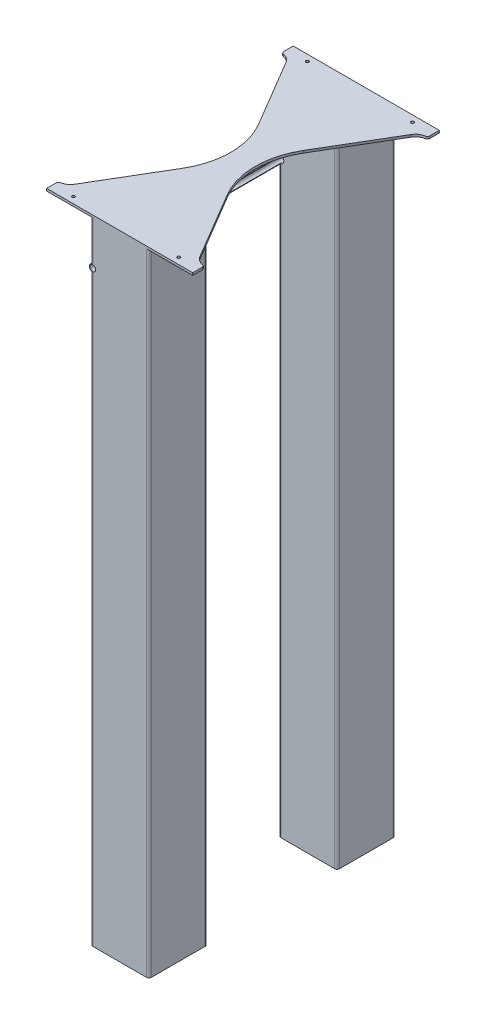
SolidWorks part; units mm, degrees
ref_plane "Front Plane" through (0, 0, 0) normal (0, 0, 1) x (1, 0, 0)
ref_plane "Top Plane" through (0, 0, 0) normal (0, 1, 0) x (1, 0, 0)
ref_plane "Right Plane" through (0, 0, 0) normal (1, 0, 0) x (0, 0, -1)
sketch "Sketch1" plane through (0, 0, 0) normal (0, 1, 0) x (1, 0, 0)
  line L0 (0, 133.985) -> (0, -133.985) construction
  line L1 (-79.375, -133.985) -> (79.375, -133.985)
  line L2 (-79.375, -133.985) -> (-79.375, -123.6187)
  line L3 (-79.375, 133.985) -> (79.375, 133.985)
  line L4 (79.375, -133.985) -> (79.375, -123.6187)
  line L5 (-79.375, -133.985) -> (79.375, 133.985) construction
  line L6 (-79.375, 133.985) -> (79.375, -133.985) construction
  line L7 (-13.1923, 0) -> (13.1923, 0) construction
  line L8 (-68.0165, 114.8119) -> (-24.5424, 41.4277)
  line L9 (-24.5424, -41.4277) -> (-68.0165, -114.8119)
  line L10 (68.0165, 114.8119) -> (24.5424, 41.4277)
  line L11 (24.5424, -41.4277) -> (68.0165, -114.8119)
  line L12 (-79.375, 123.6187) -> (-79.375, 133.985)
  line L13 (79.375, 123.6187) -> (79.375, 133.985)
  circle A0 centre (-57.15, 127) radius 1.5875
  circle A1 centre (57.15, 127) radius 1.5875
  arc A2 (-77.2448, 121.112) -> (-68.0165, 114.8119) centre (-79.375, 108.083) cw
  arc A3 (-24.5424, 41.4277) -> (-24.5424, -41.4277) centre (-94.4723, 0) cw
  arc A4 (-68.0165, -114.8119) -> (-77.2448, -121.112) centre (-79.375, -108.083) cw
  circle A5 centre (57.15, -127) radius 1.5875
  circle A6 centre (-57.15, -127) radius 1.5875
  arc A7 (77.2448, 121.112) -> (68.0165, 114.8119) centre (79.375, 108.083) ccw
  arc A8 (24.5424, 41.4277) -> (24.5424, -41.4277) centre (94.4723, 0) ccw
  arc A9 (68.0165, -114.8119) -> (77.2448, -121.112) centre (79.375, -108.083) ccw
  arc A10 (-77.2448, 121.112) -> (-79.375, 123.6187) centre (-76.835, 123.6187) cw
  arc A11 (77.2448, 121.112) -> (79.375, 123.6187) centre (76.835, 123.6187) ccw
  arc A12 (77.2448, -121.112) -> (79.375, -123.6187) centre (76.835, -123.6187) cw
  arc A13 (-77.2448, -121.112) -> (-79.375, -123.6187) centre (-76.835, -123.6187) ccw
  point P0 (0, 0)
  point P40 (-79.375, 121.285)
  point P43 (79.375, 121.285)
  point P46 (79.375, -121.285)
  point P49 (-79.375, -121.285)
  dimension "D3" = 3.175
  dimension "D9" = 81.28
  dimension "D10" = 2.54
  dimension "D1" = 158.75
  dimension "D2" = 267.97
  dimension "D4" = 114.3
  dimension "D5" = 114.3
  dimension "D6" = 6.985
  dimension "D7" = 12.7
  dimension "D8" = 12.7
extrude "Boss-Extrude1" add sketch "Sketch1" against normal blind 2.54
sketch "Sketch2" plane through (0, -2.54, 0) normal (0, -1, 0) x (1, 0, 0)
  line L0 (0, 133.985) -> (0, -133.985) construction
  line L1 (-13.1923, 0) -> (13.1923, 0) construction
  line L2 (-31.75, -133.985) -> (31.75, -133.985)
  line L3 (-31.75, 70.485) -> (31.75, 70.485)
  line L4 (-31.75, 70.485) -> (-31.75, 133.985)
  line L5 (-31.75, 133.985) -> (31.75, 133.985)
  line L6 (31.75, 70.485) -> (31.75, 133.985)
  line L7 (-31.75, 70.485) -> (31.75, 133.985) construction
  line L8 (-31.75, 133.985) -> (31.75, 70.485) construction
  line L9 (31.75, -70.485) -> (31.75, -133.985)
  line L10 (-79.375, 133.985) -> (-79.375, 123.6187)
  line L11 (79.375, 133.985) -> (-79.375, 133.985)
  line L12 (79.375, 123.6187) -> (79.375, 133.985)
  line L13 (24.5424, 41.4277) -> (68.0165, 114.8119)
  line L14 (68.0165, -114.8119) -> (24.5424, -41.4277)
  line L15 (79.375, -133.985) -> (79.375, -123.6187)
  line L16 (-79.375, -133.985) -> (79.375, -133.985)
  line L17 (-79.375, -123.6187) -> (-79.375, -133.985)
  line L18 (-24.5424, -41.4277) -> (-68.0165, -114.8119)
  line L19 (-68.0165, 114.8119) -> (-24.5424, 41.4277)
  line L20 (-79.375, 133.985) -> (-79.375, 123.6187) construction
  line L21 (79.375, 133.985) -> (-79.375, 133.985) construction
  line L22 (79.375, 123.6187) -> (79.375, 133.985) construction
  line L23 (24.5424, 41.4277) -> (68.0165, 114.8119) construction
  line L24 (68.0165, -114.8119) -> (24.5424, -41.4277) construction
  line L25 (79.375, -133.985) -> (79.375, -123.6187) construction
  line L26 (-79.375, -133.985) -> (79.375, -133.985) construction
  line L27 (-79.375, -123.6187) -> (-79.375, -133.985) construction
  line L28 (-24.5424, -41.4277) -> (-68.0165, -114.8119) construction
  line L29 (-68.0165, 114.8119) -> (-24.5424, 41.4277) construction
  line L30 (-31.75, -70.485) -> (31.75, -70.485)
  line L31 (-31.75, -70.485) -> (-31.75, -133.985)
  circle A1 centre (57.15, -127) radius 1.5875
  circle A2 centre (57.15, -127) radius 1.5875 construction
  circle A3 centre (-57.15, -127) radius 1.5875
  circle A4 centre (-57.15, -127) radius 1.5875 construction
  circle A5 centre (-57.15, 127) radius 1.5875
  circle A6 centre (-57.15, 127) radius 1.5875 construction
  circle A7 centre (57.15, 127) radius 1.5875
  circle A8 centre (57.15, 127) radius 1.5875 construction
  arc A18 (77.2448, 121.112) -> (79.375, 123.6187) centre (76.835, 123.6187) ccw
  arc A19 (77.2448, 121.112) -> (68.0165, 114.8119) centre (79.375, 108.083) ccw
  arc A20 (24.5424, 41.4277) -> (24.5424, -41.4277) centre (94.4723, 0) ccw
  arc A21 (68.0165, -114.8119) -> (77.2448, -121.112) centre (79.375, -108.083) ccw
  arc A22 (79.375, -123.6187) -> (77.2448, -121.112) centre (76.835, -123.6187) ccw
  arc A23 (-77.2448, -121.112) -> (-79.375, -123.6187) centre (-76.835, -123.6187) ccw
  arc A24 (-77.2448, -121.112) -> (-68.0165, -114.8119) centre (-79.375, -108.083) ccw
  arc A25 (-24.5424, -41.4277) -> (-24.5424, 41.4277) centre (-94.4723, 0) ccw
  arc A26 (-68.0165, 114.8119) -> (-77.2448, 121.112) centre (-79.375, 108.083) ccw
  arc A27 (-79.375, 123.6187) -> (-77.2448, 121.112) centre (-76.835, 123.6187) ccw
  arc A28 (77.2448, 121.112) -> (79.375, 123.6187) centre (76.835, 123.6187) ccw construction
  arc A29 (77.2448, 121.112) -> (68.0165, 114.8119) centre (79.375, 108.083) ccw construction
  arc A30 (24.5424, 41.4277) -> (24.5424, -41.4277) centre (94.4723, 0) ccw construction
  arc A31 (68.0165, -114.8119) -> (77.2448, -121.112) centre (79.375, -108.083) ccw construction
  arc A32 (79.375, -123.6187) -> (77.2448, -121.112) centre (76.835, -123.6187) ccw construction
  arc A33 (-77.2448, -121.112) -> (-79.375, -123.6187) centre (-76.835, -123.6187) ccw construction
  arc A34 (-77.2448, -121.112) -> (-68.0165, -114.8119) centre (-79.375, -108.083) ccw construction
  arc A35 (-24.5424, -41.4277) -> (-24.5424, 41.4277) centre (-94.4723, 0) ccw construction
  arc A36 (-68.0165, 114.8119) -> (-77.2448, 121.112) centre (-79.375, 108.083) ccw construction
  arc A37 (-79.375, 123.6187) -> (-77.2448, 121.112) centre (-76.835, 123.6187) ccw construction
  point P34 (0, 102.235)
  dimension "D6" = 63.5
  dimension "D7" = 63.5
  dimension "D1" = 0
  dimension "D2" = 0
  dimension "D3" = 0
  dimension "D4" = 0
  dimension "D5" = 0
extrude "Boss-Extrude2" add sketch "Sketch2" along normal blind 685.8
shell "Shell1" thickness 2.54 removed face at (0, -688.34, -102.235) removed face at (0, -688.34, 102.235)
fillet "Fillet1" radius 2.54 4 edges at (-31.75, -345.44, 70.485) (-31.75, -345.44, 133.985) (31.75, -345.44, 70.485) (31.75, -345.44, 133.985)
fillet "Fillet2" radius 2.54 4 edges at (31.75, -345.44, -70.485) (31.75, -345.44, -133.985) (-31.75, -345.44, -133.985) (-31.75, -345.44, -70.485)
ref_plane "Plane1" through (0, -510.54, 0) normal (0, -1, 0) x (-1, 0, 0)
ref_plane "Plane3" through (400.05, 0, 0) normal (-1, 0, 0) x (0, 0, 1)
sketch "Sketch4" plane through (0, 0, -133.985) normal (0, 0, -1) x (-1, 0, 0)
  line L0 (29.21, -688.34) -> (29.21, -2.54) construction
  line L1 (0, 0) -> (0, -50.038) construction
  line L2 (-79.375, 0) -> (79.375, 0) construction
  circle A0 centre (29.21, -50.038) radius 3.175
  line M8 (29.21, -688.34) -> (29.21, -2.54)
  dimension "D1" = 6.35
  dimension "D2" = 50.038
extrude "Cut-Extrude1" cut sketch "Sketch4" along direction (0, 0, 1) on the side against the normal up to vertex (267.97 mm away) contours A0 M8 | A0 M8 region at (-30.5575, -50.038, -133.985) region at (-27.8625, -50.038, -133.985) up to point (-29.21, -2.54, 133.985)
sketch "Sketch6" plane through (0, 0, -133.985) normal (0, 0, -1) x (-1, 0, 0)
  line L0 (29.21, -46.863) -> (29.21, -46.228)
  line L1 (29.21, -53.213) -> (29.21, -53.848)
  arc A0 (29.21, -53.213) -> (31.75, -51.943) centre (29.21, -50.038) ccw construction
  arc A1 (31.75, -48.133) -> (29.21, -46.863) centre (29.21, -50.038) ccw construction
  arc A3 (29.21, -53.213) -> (31.75, -51.943) centre (29.21, -50.038) ccw construction
  arc A4 (31.75, -48.133) -> (29.21, -46.863) centre (29.21, -50.038) ccw construction
  arc A6 (29.21, -53.848) -> (29.21, -46.228) centre (29.21, -50.038) ccw
  arc A7 (29.21, -53.213) -> (29.21, -46.863) centre (29.21, -50.038) ccw
  dimension "D1" = 7.62
extrude "Boss-Extrude4" add sketch "Sketch6" against normal blind 27.94
sketch "Sketch7" plane through (0, 0, -106.045) normal (0, 0, 1) x (1, 0, 0)
  line L0 (-31.75, -688.34) -> (-31.75, -51.943) construction
  line L1 (-31.75, -688.34) -> (-31.75, -51.943) construction
  line L2 (-31.75, -60.0065) -> (-31.75, -59.2181)
  line L3 (-31.75, -40.0695) -> (-31.75, -40.8579)
  line L4 (-31.75, -48.133) -> (-31.75, -2.54) construction
  line L5 (-31.75, -40.8579) -> (-31.75, -47.1982)
  line L6 (-31.75, -59.2181) -> (-31.75, -52.8778)
  arc A0 (-31.75, -48.133) -> (-31.75, -51.943) centre (-29.21, -50.038) ccw construction
  arc A1 (-31.75, -47.1982) -> (-31.75, -52.8778) centre (-29.21, -50.038) ccw construction
  arc A2 (-31.75, -48.133) -> (-31.75, -51.943) centre (-29.21, -50.038) ccw construction
  arc A3 (-31.75, -47.1982) -> (-31.75, -52.8778) centre (-29.21, -50.038) ccw construction
  arc A4 (-31.75, -40.8579) -> (-31.75, -59.2181) centre (-29.21, -50.038) ccw
  arc A5 (-31.75, -40.0695) -> (-31.75, -60.0065) centre (-29.21, -50.038) ccw
  circle A6 centre (-29.21, -50.038) radius 3.175
  arc A7 (-31.75, -52.8778) -> (-31.75, -47.1982) centre (-29.21, -50.038) cw
  arc M3 (-31.75, -47.1982) -> (-31.75, -52.8778) centre (-29.21, -50.038) ccw
  line M4 (-31.75, -52.8778) -> (-31.75, -51.943)
  arc M5 (-31.75, -51.943) -> (-31.75, -48.133) centre (-29.21, -50.038) cw
  line M6 (-31.75, -48.133) -> (-31.75, -47.1982)
  dimension "D1" = 19.05
  dimension "D2" = 0.762
extrude "Boss-Extrude5" add sketch "Sketch7" along normal blind 10.16 contours A5 A4 region at (-39.2831, -50.038, -106.045)
extrude "Boss-Extrude6" add sketch "Sketch7<2>" against normal blind 0.762 contours A4 M3 M6 M5 M4 | A5 A4 region at (-39.2831, -50.038, -106.045) region at (-34.7891, -50.038, -106.045)
sketch "Sketch7<2>" plane through (0, 0, -106.045) normal (0, 0, 1) x (1, 0, 0) same geometry as "Sketch7"
sketch "Sketch8" plane through (0, 0, -95.885) normal (0, 0, 1) x (1, 0, 0)
  line L0 (-31.75, -688.34) -> (-31.75, -51.943) construction
  line L1 (-31.75, -48.133) -> (-31.75, -2.54) construction
  line L2 (-31.75, -40.0695) -> (-31.75, -40.8579) construction
  line L3 (-31.75, -688.34) -> (-31.75, -51.943) construction
  line L4 (-31.75, -48.133) -> (-31.75, -2.54) construction
  line L5 (-31.75, -40.0695) -> (-31.75, -40.8579) construction
  line L6 (-31.75, -40.0695) -> (-31.75, -48.133)
  line L7 (-31.75, -51.943) -> (-31.75, -60.0065)
  arc A0 (-31.75, -40.0695) -> (-31.75, -60.0065) centre (-29.21, -50.038) ccw construction
  arc A1 (-31.75, -40.0695) -> (-31.75, -60.0065) centre (-29.21, -50.038) ccw construction
  arc A2 (-31.75, -60.0065) -> (-31.75, -40.0695) centre (-29.21, -50.038) cw
  arc A3 (-31.75, -48.133) -> (-31.75, -51.943) centre (-29.21, -50.038) ccw construction
  arc A4 (-31.75, -48.133) -> (-31.75, -51.943) centre (-29.21, -50.038) ccw construction
  arc A5 (-31.75, -48.133) -> (-31.75, -51.943) centre (-29.21, -50.038) ccw
extrude "Boss-Extrude7" add sketch "Sketch8" along normal blind 0.762
sketch "Sketch9" plane through (0, 0, -95.123) normal (0, 0, 1) x (1, 0, 0)
  line L0 (-29.21, -46.228) -> (-29.21, -46.863)
  line L1 (-29.21, -53.848) -> (-29.21, -53.213)
  arc A0 (-31.75, -51.943) -> (-29.21, -53.213) centre (-29.21, -50.038) ccw construction
  arc A2 (-29.21, -46.863) -> (-31.75, -48.133) centre (-29.21, -50.038) ccw construction
  arc A3 (-31.75, -48.133) -> (-31.75, -51.943) centre (-29.21, -50.038) ccw construction
  arc A4 (-31.75, -51.943) -> (-29.21, -53.213) centre (-29.21, -50.038) ccw
  arc A6 (-29.21, -46.863) -> (-31.75, -48.133) centre (-29.21, -50.038) ccw
  arc A7 (-31.75, -48.133) -> (-31.75, -51.943) centre (-29.21, -50.038) ccw
  arc A8 (-29.21, -46.228) -> (-29.21, -53.848) centre (-29.21, -50.038) ccw construction
  arc A9 (-29.21, -46.228) -> (-29.21, -53.848) centre (-29.21, -50.038) ccw
extrude "Boss-Extrude8" add sketch "Sketch9" along normal up to vertex up to point (-29.21, -53.213, 133.985)
sketch "Sketch12" plane through (0, 0, -95.885) normal (0, 0, -1) x (-1, 0, 0)
  line L0 (29.21, -688.34) -> (29.21, -53.213) construction
  line L1 (31.75, -40.5775) -> (29.21, -40.5775)
  line L2 (31.75, -40.5775) -> (31.75, -59.4985)
  line L3 (31.75, -59.4985) -> (29.21, -59.4985)
  line L4 (29.21, -40.5775) -> (29.21, -59.4985)
  line L5 (30.48, -59.4985) -> (30.48, -40.5775) construction
  line L6 (31.75, -50.038) -> (29.21, -50.038) construction
  line L8 (31.75, -40.0695) -> (31.75, -40.8579) construction
  point P17 (31.75, -40.4637)
  point P364 (30.48, -50.038)
  dimension "D1" = 0.508
  dimension "D2" = 0.508
extrude "Cut-Extrude2" cut sketch "Sketch12" along normal up to vertex (10.16 mm away) up to point (-31.75, -47.1982, -106.045)
